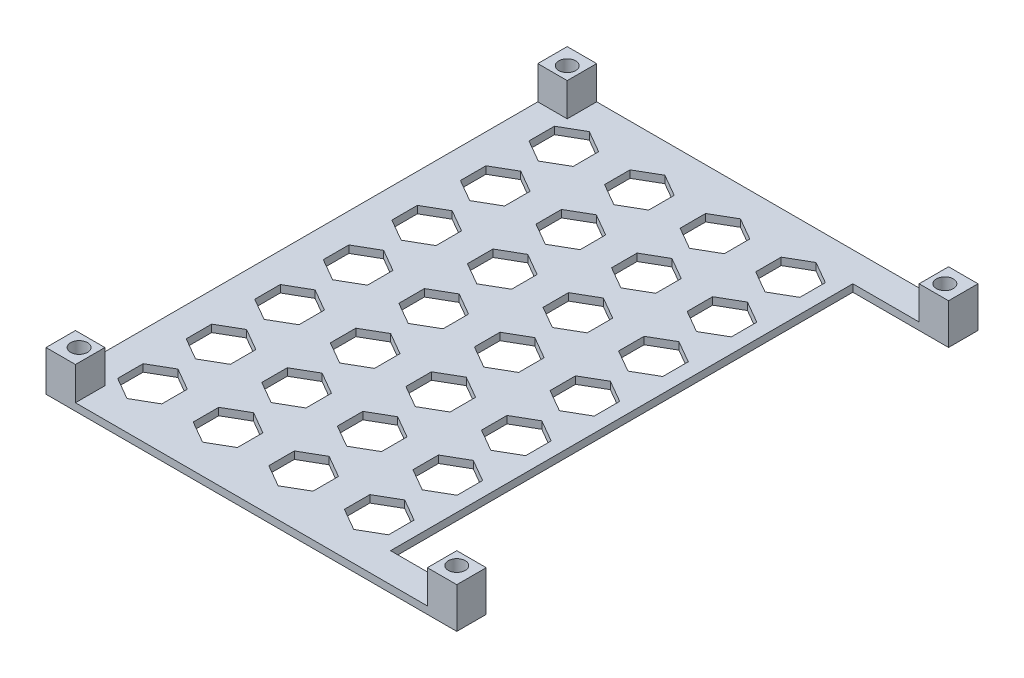
SolidWorks part; units mm, degrees
ref_plane "Front Plane" through (0, 0, 0) normal (0, 0, 1) x (1, 0, 0)
ref_plane "Top Plane" through (0, 0, 0) normal (0, 1, 0) x (1, 0, 0)
ref_plane "Right Plane" through (0, 0, 0) normal (1, 0, 0) x (0, 0, -1)
sketch "Sketch1" plane through (0, 0, 0) normal (0, 1, 0) x (1, 0, 0)
  line L0 (0, 0) -> (55.8, 0)
  line L5 (55.8, 0) -> (55.8, 4)
  line L6 (55.8, 4) -> (42.8, 4)
  line L7 (42.8, 4) -> (42.8, 66.8)
  line L8 (42.8, 66.8) -> (55.8, 66.8)
  line L9 (55.8, 66.8) -> (55.8, 70.8)
  line L10 (55.8, 70.8) -> (0, 70.8)
  line L11 (0, 70.8) -> (0, 0)
  dimension "D1" = 55.8
  dimension "D2" = 13
  dimension "D3" = 70.8
  dimension "D4" = 4
  dimension "D5" = 4
extrude "Boss-Extrude1" add sketch "Sketch1" along normal blind 1
sketch "Sketch2" plane through (0, 1, 0) normal (0, 1, 0) x (1, 0, 0)
  line L0 (42.8, 66.8) -> (0, 66.8) construction
  line L1 (0, 70.8) -> (0, 0) construction
  line L2 (4, 70.8) -> (4, 0) construction
  line L3 (55.8, 70.8) -> (0, 70.8) construction
  line L5 (0, 0) -> (55.8, 0) construction
  line L6 (40.8, 66.8) -> (40.8, 0) construction
  line L7 (42.8, 4) -> (42.8, 66.8) construction
  line L9 (7, 66.8) -> (4, 65.0679)
  line L10 (4, 65.0679) -> (4, 61.6038)
  line L11 (4, 61.6038) -> (7, 59.8718)
  line L12 (7, 59.8718) -> (10, 61.6038)
  line L13 (10, 61.6038) -> (10, 65.0679)
  line L14 (10, 65.0679) -> (7, 66.8)
  circle A0 centre (7, 63.3359) radius 3 construction
  dimension "D1" = 4
  dimension "D2" = 2
  dimension "D3" = 6
extrude "Cut-Extrude1" cut sketch "Sketch2" against normal up to surface (1 mm away) up to face at (38.6, 0, -35.4)
pattern_linear "LPattern1" count 4 spacing 10.2667 along (1, 0, 0) count 7 spacing 9.312 along (0, 0, 1) of "Cut-Extrude1"
sketch "Sketch3" plane through (0, 1, 0) normal (0, 1, 0) x (1, 0, 0)
  line L0 (42.8, 66.8) -> (55.8, 66.8) construction
  line L1 (0, 70.8) -> (4, 70.8)
  line L2 (0, 70.8) -> (0, 66.8)
  line L3 (0, 66.8) -> (4, 66.8)
  line L4 (4, 70.8) -> (4, 66.8)
  line L5 (55.8, 70.8) -> (51.8, 70.8)
  line L6 (55.8, 70.8) -> (55.8, 66.8)
  line L7 (55.8, 66.8) -> (51.8, 66.8)
  line L8 (51.8, 70.8) -> (51.8, 66.8)
  line L9 (0, 0) -> (55.8, 0) construction
  line L10 (55.8, 4) -> (51.8, 4)
  line L11 (55.8, 4) -> (55.8, 0)
  line L12 (55.8, 0) -> (51.8, 0)
  line L13 (51.8, 4) -> (51.8, 0)
  line L15 (0, 0) -> (4, 0)
  line L16 (0, 0) -> (0, 4)
  line L17 (0, 4) -> (4, 4)
  line L18 (4, 0) -> (4, 4)
  dimension "D1" = 4
extrude "Boss-Extrude2" add sketch "Sketch3" along normal blind 4.5
sketch "Sketch4" plane through (0, 5.5, 0) normal (0, 1, 0) x (1, 0, 0)
  line L3 (0, 68.55) -> (55.8, 68.55) construction
  line L4 (0, 70.8) -> (0, 66.8) construction
  line L5 (55.8, 66.8) -> (55.8, 70.8) construction
  line L6 (4, 70.8) -> (0, 70.8) construction
  circle A0 centre (2.25, 68.55) radius 1.15
  circle A1 centre (53.55, 68.55) radius 1.15
  dimension "D3" = 2.3
  dimension "D1" = 2.25
  dimension "D2" = 2.25
  dimension "D4" = 2.25
extrude "Cut-Extrude2" cut sketch "Sketch4" against normal up to surface (5.5 mm away) up to face at (17.2667, 0, -63.3359)
ref_plane "Plane1" through (0, 0, -35.4) normal (0, 0, -1) x (-1, 0, 0)
mirror "Mirror1" about plane through (0, 0, -35.4) normal (0, 0, -1) of "Cut-Extrude2"
